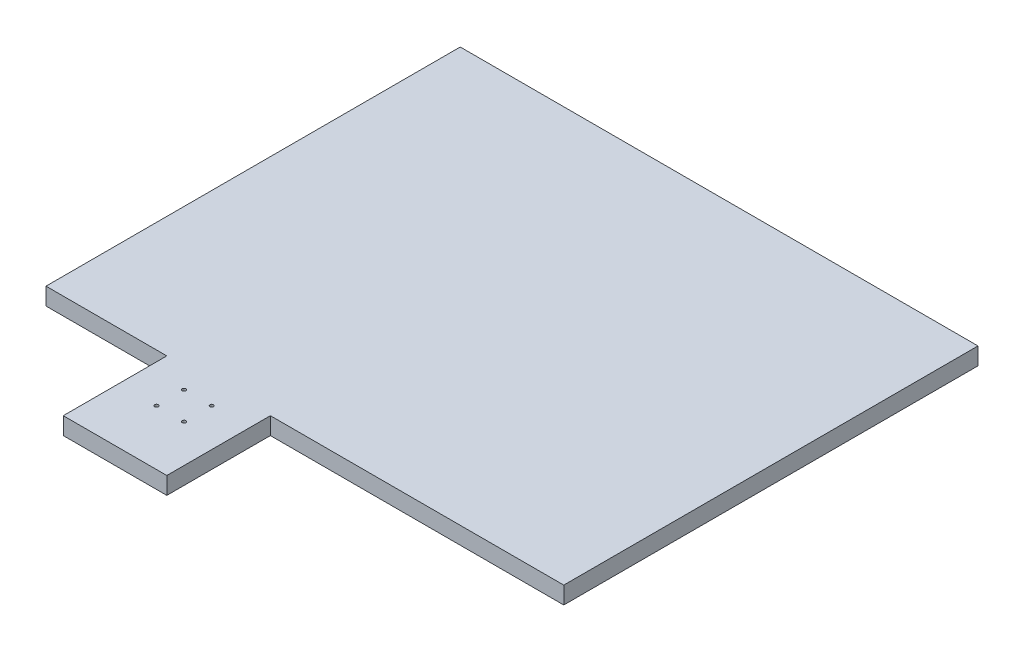
SolidWorks part; units mm, degrees
ref_plane "前基準面" through (0, 0, 0) normal (0, 0, 1) x (1, 0, 0)
ref_plane "上基準面" through (0, 0, 0) normal (0, 1, 0) x (1, 0, 0)
ref_plane "右基準面" through (0, 0, 0) normal (1, 0, 0) x (0, 0, -1)
sketch "草圖1" plane through (0, 0, 0) normal (0, 1, 0) x (1, 0, 0)
  line L0 (-50, -987.0204) -> (-50, 49012.9796) construction
  line L1 (-150, -120) -> (-80, -120)
  line L2 (-150, -120) -> (-150, 120)
  line L3 (-150, 120) -> (150, 120)
  line L4 (150, -120) -> (150, 120)
  line L5 (-150, -120) -> (150, 120) construction
  line L6 (-150, 120) -> (150, -120) construction
  line L7 (-80, -120) -> (-80, -180)
  line L8 (-80, -180) -> (-20, -180)
  line L9 (-20, -180) -> (-20, -120)
  line L10 (-20, -120) -> (150, -120)
  point P0 (0, 0)
  point P10 (-50, -180)
  dimension "D1" = 300
  dimension "D2" = 240
  dimension "D3" = 200
  dimension "D4" = 60
  dimension "D5" = 60
extrude "填料-伸長1" add sketch "草圖1" along normal blind 10
sketch "草圖2" plane through (0, 0, 0) normal (0, -1, 0) x (1, 0, 0)
  line L0 (-50, -820) -> (-50, 49180) construction
  line L1 (-80, 180) -> (-20, 180) construction
  line L2 (-1080, 140) -> (48920, 140) construction
  line L3 (-80, 120) -> (-80, 180) construction
  line L4 (-150, 120) -> (-80, 120) construction
  line L6 (-40, 150) -> (-60, 150)
  line L7 (-40, 150) -> (-40, 130)
  line L8 (-40, 130) -> (-60, 130)
  line L9 (-60, 150) -> (-60, 130)
  line L10 (-40, 150) -> (-60, 130) construction
  line L11 (-40, 130) -> (-60, 150) construction
  circle A0 centre (-58, 132) radius 1.05
  circle A1 centre (-58, 148) radius 1.05
  circle A2 centre (-42, 148) radius 1.05
  circle A3 centre (-42, 132) radius 1.05
  point P5 (-50, 180)
  point P10 (-80, 150)
  point P20 (-50, 140)
  dimension "D1" = 2.1
  dimension "D2" = 20
  dimension "D3" = 8
  dimension "D4" = 8
  dimension "D5" = 20
  dimension "D6" = 20
extrude "除料-伸長2" cut sketch "草圖2" against normal blind 8 contours L6 L9 L8 L7 A1 A0 A2 A3 region at (-50, 0, 140)
extrude "除料-伸長3" cut sketch "草圖2<3>" against normal through all contours A3 | A0 | A1 | A2 region at (-58, 0, 132) region at (-58, 0, 148) region at (-42, 0, 148) region at (-42, 0, 132)
sketch "草圖2<3>" plane through (0, 0, 0) normal (0, -1, 0) x (1, 0, 0) same geometry as "草圖2"
